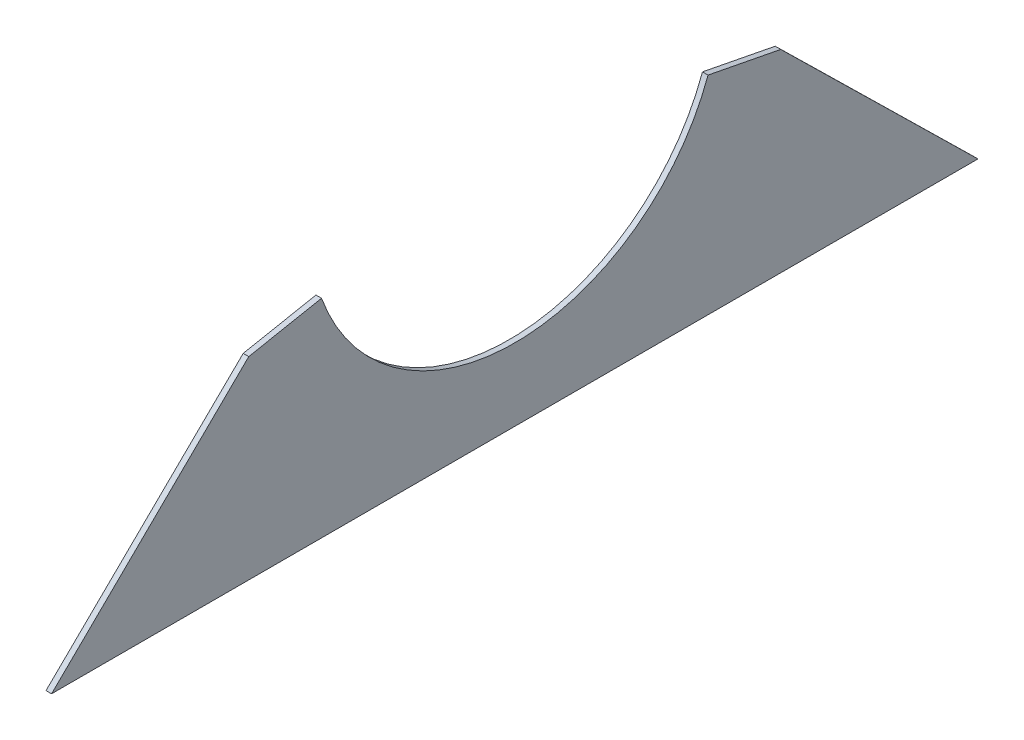
SolidWorks part; units mm, degrees
material "AISI 304"
ref_plane "Спереди" through (0, 0, 0) normal (0, 0, 1) x (1, 0, 0)
ref_plane "Сверху" through (0, 0, 0) normal (0, 1, 0) x (1, 0, 0)
ref_plane "Справа" through (0, 0, 0) normal (1, 0, 0) x (0, 0, -1)
sketch "Эскиз1" plane through (0, 0, 0) normal (1, 0, 0) x (0, 0, -1)
  line L0 (-111, 0) -> (111, 0) construction
  line L2 (250, -150) -> (-250, -150)
  line L4 (0, 0) -> (0, -150) construction
  line L5 (-250, -150) -> (-104.3059, -37.9642) construction
  line L6 (-104.3059, -37.9642) -> (0, 0) construction
  line L7 (104.3059, -37.9642) -> (250, -150) construction
  line L8 (0, 0) -> (104.3059, -37.9642) construction
  line L9 (-104.3059, -37.9642) -> (-143.571, -45.5966)
  line L10 (-143.571, -45.5966) -> (-250, -150)
  line L11 (143.571, -45.5966) -> (250, -150)
  line L12 (104.3059, -37.9642) -> (143.571, -45.5966)
  arc A0 (-104.3059, -37.9642) -> (104.3059, -37.9642) centre (0, 0) ccw
  dimension "D1" = 500
  dimension "D2" = 111
  dimension "D3" = 150
  dimension "D4" = 140
  dimension "D5" = 158
  dimension "D6" = 40
base flange "Базовая кромка1" sketch "Эскиз1" thickness 3 reverse thickness direction no parameters "D1"=4
sketch "Сгиб-Линии1" plane through (0, 0, 0) normal (0, 1, 0) x (1, 0, 0)
sketch "Граничная рамка1" plane through (0, 0, 0) normal (0, 1, 0) x (1, 0, 0)
sheet metal parameters "Листовой металл3" thickness 3 parameters "D1"=4
flat pattern "Развертка3" [suppressed]
sketch "Сгиб-Линии2" plane through (0, 0, 0) normal (0, 1, 0) x (1, 0, 0)
sketch "Граничная рамка2" [suppressed] plane through (0, 0, 0) normal (0, 1, 0) x (1, 0, 0)
